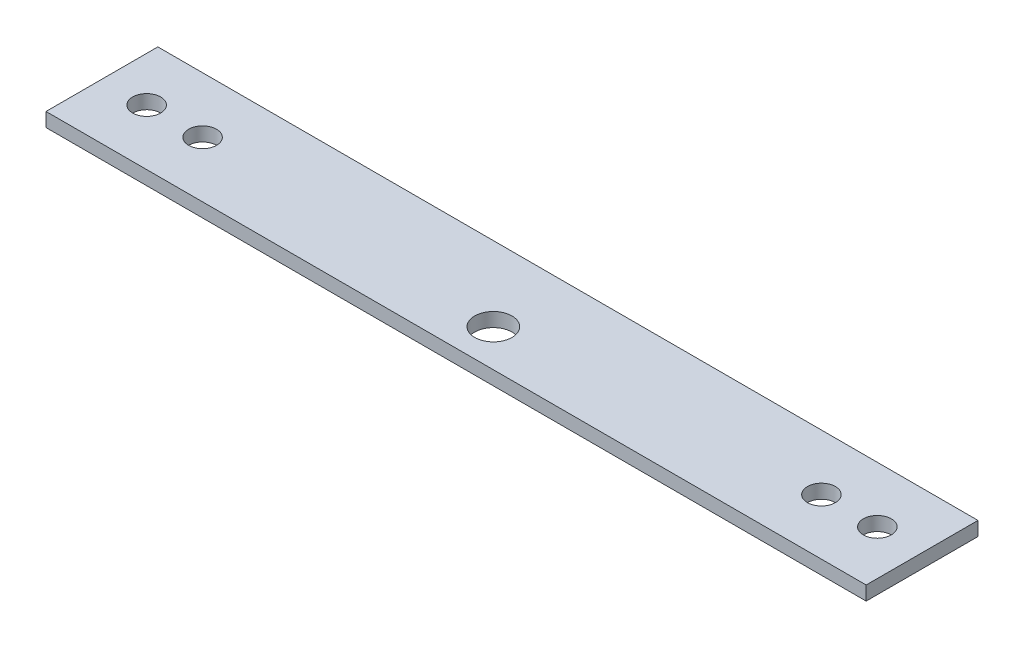
SolidWorks part; units mm, degrees
ref_plane "Front Plane" through (0, 0, 0) normal (0, 0, 1) x (1, 0, 0)
ref_plane "Top Plane" through (0, 0, 0) normal (0, 1, 0) x (1, 0, 0)
ref_plane "Right Plane" through (0, 0, 0) normal (1, 0, 0) x (0, 0, -1)
sketch "Sketch2" plane through (0, 0, 0) normal (0, 1, 0) x (1, 0, 0)
  line L1 (-139.7, -19.05) -> (139.7, -19.05)
  line L2 (-139.7, -19.05) -> (-139.7, 19.05)
  line L3 (-139.7, 19.05) -> (139.7, 19.05)
  line L4 (139.7, -19.05) -> (139.7, 19.05)
  line L5 (0, 19.05) -> (0, -19.05) construction
  line L6 (-139.7, 0) -> (139.7, 0) construction
  circle A0 centre (-124.46, 0) radius 4.7625
  circle A1 centre (-105.41, 0) radius 4.7625
  circle A2 centre (124.46, 0) radius 4.7625
  circle A3 centre (105.41, 0) radius 4.7625
  circle A4 centre (0, -6.35) radius 6.35
  point P0 (0, 0)
  dimension "D3" = 9.525
  dimension "D6" = 12.7
  dimension "D1" = 38.1
  dimension "D2" = 279.4
  dimension "D4" = 19.05
  dimension "D5" = 15.24
  dimension "D7" = 12.7
extrude "Boss-Extrude1" add sketch "Sketch2" along normal blind 4.7625
